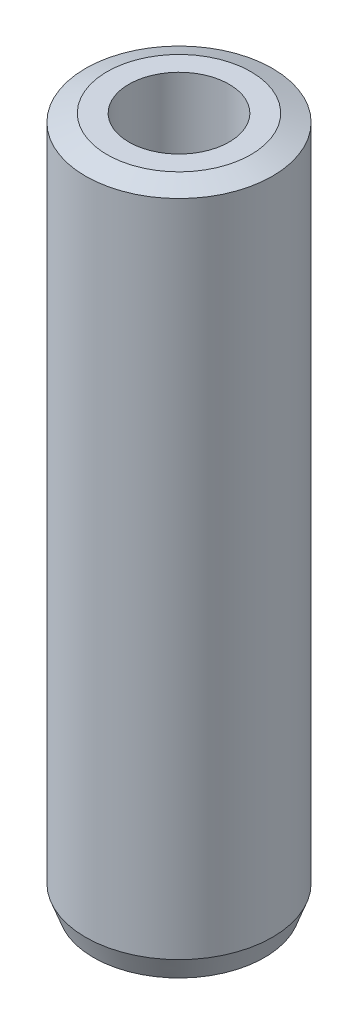
SolidWorks part; units mm, degrees
ref_plane "Front Plane" through (0, 0, 0) normal (0, 0, 1) x (1, 0, 0)
ref_plane "Top Plane" through (0, 0, 0) normal (0, 1, 0) x (1, 0, 0)
ref_plane "Right Plane" through (0, 0, 0) normal (1, 0, 0) x (0, 0, -1)
sketch "Sketch1" plane through (0, 0, 0) normal (0, 1, 0) x (1, 0, 0)
  circle A0 centre (0, 0) radius 25
  dimension "SHAFT_OD" = 50
extrude "Boss-Extrude1" add sketch "Sketch1" along normal blind 184.2469
sketch "Sketch2" plane through (0, 0, 0) normal (0, 1, 0) x (1, 0, 0)
  circle A0 centre (0, 0) radius 13.4151
  dimension "BORE_D" = 26.8302
extrude "Cut-Extrude1" cut sketch "Sketch2" along normal through all
chamfer "Chamfer1" distance 2.115 angle 69.809 2 edges at (0, 184.2469, 25) (0, 0, 25) first distance on face at (0, 184.2469, 25) first distance on face at (0, 0, 13.4151)
